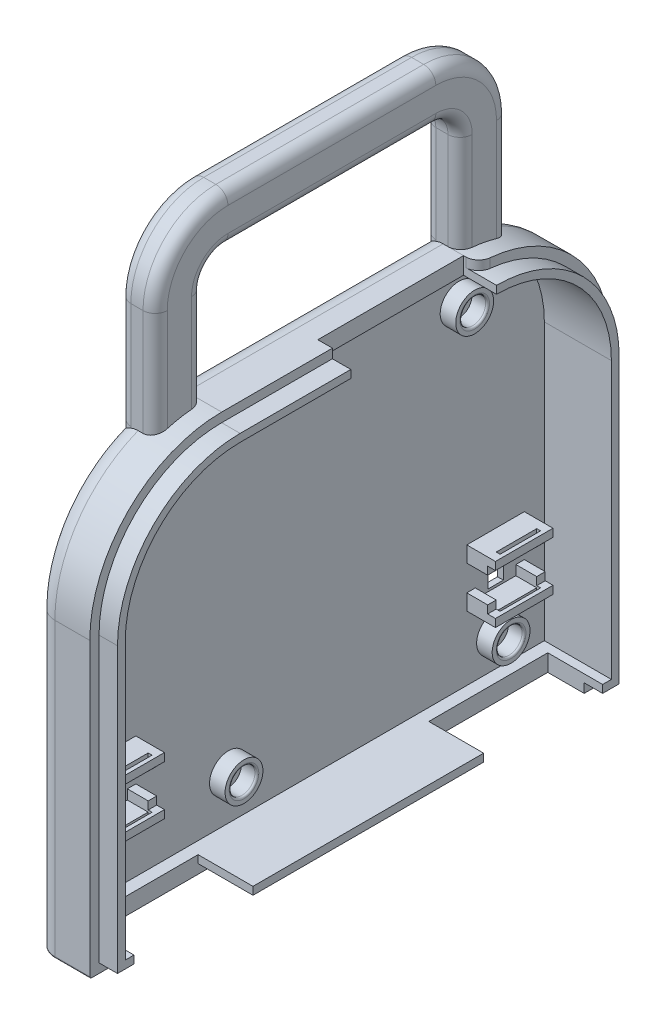
SolidWorks part; units mm, degrees
ref_plane "Front Plane" through (0, 0, 0) normal (0, 0, 1) x (1, 0, 0)
ref_plane "Top Plane" through (0, 0, 0) normal (0, 1, 0) x (1, 0, 0)
ref_plane "Right Plane" through (0, 0, 0) normal (1, 0, 0) x (0, 0, -1)
sketch "Sketch1" plane through (0, 0, 0) normal (1, 0, 0) x (0, 0, -1)
  line L0 (-52.8, 99.65) -> (52.8, 99.65)
  line L1 (-107.1, 45.35) -> (-107.1, -45.35)
  line L2 (-70, -75.35) -> (70, -75.35)
  line L3 (107.1, 45.35) -> (107.1, -45.35)
  line L4 (107.1, 0) -> (-107.1, 0) construction
  line L5 (0, 99.65) -> (0, -75.35) construction
  line L11 (107.1, -45.35) -> (107.1, -75.35)
  line L12 (107.1, -75.35) -> (70, -75.35)
  line L13 (-83.2, -21.7) -> (-76.8, -21.7)
  line L14 (-83.2, -21.7) -> (-83.2, -38.3)
  line L15 (-83.2, -38.3) -> (-76.8, -38.3)
  line L16 (-76.8, -21.7) -> (-76.8, -38.3)
  line L17 (-83.2, -21.7) -> (-76.8, -38.3) construction
  line L18 (-83.2, -38.3) -> (-76.8, -21.7) construction
  line L19 (76.8, -21.7) -> (83.2, -21.7)
  line L20 (76.8, -21.7) -> (76.8, -38.3)
  line L21 (76.8, -38.3) -> (83.2, -38.3)
  line L22 (83.2, -21.7) -> (83.2, -38.3)
  line L23 (76.8, -21.7) -> (83.2, -38.3) construction
  line L24 (76.8, -38.3) -> (83.2, -21.7) construction
  line L25 (80, -30) -> (-80, -30) construction
  line L27 (-107.1, -45.35) -> (-107.1, -75.35)
  line L28 (-107.1, -75.35) -> (-70, -75.35)
  arc A0 (52.8, 99.65) -> (107.1, 45.35) centre (52.8, 45.35) cw
  arc A1 (-52.8, 99.65) -> (-107.1, 45.35) centre (-52.8, 45.35) ccw
  point P16 (0, 0)
  point P17 (-80, -30)
  point P32 (80, -30)
  point P39 (-80, -30)
  point P40 (0, -30)
  dimension "D4" = 54.3
  dimension "D2" = 175
  dimension "D3" = 214.2
  dimension "D5" = 140
  dimension "D6" = 30
  dimension "D7" = 160
  dimension "D8" = 6.4
  dimension "D9" = 16.6
  dimension "D10" = 6.4
  dimension "D11" = 16.6
  dimension "D12" = 30
extrude "Boss-Extrude1" add sketch "Sketch1" along normal blind 2.4
sketch "Sketch9" plane through (2.4, 0, 0) normal (1, 0, 0) x (0, 0, -1)
  line L17 (52.8, 99.65) -> (-52.8, 99.65)
  line L31 (52.8, 99.65) -> (-52.8, 99.65)
  line L32 (-107.1, 45.35) -> (-107.1, -75.35)
  line L33 (-107.1, 45.35) -> (-107.1, -75.35)
  line L34 (-107.1, -75.35) -> (107.1, -75.35)
  line L39 (107.1, -75.35) -> (107.1, 45.35)
  line L43 (107.1, -75.35) -> (107.1, 45.35)
  line L45 (-107.1, -75.35) -> (107.1, -75.35)
  arc A15 (-52.8, 99.65) -> (-107.1, 45.35) centre (-52.8, 45.35) ccw
  arc A16 (-52.8, 99.65) -> (-107.1, 45.35) centre (-52.8, 45.35) ccw
  arc A17 (107.1, 45.35) -> (52.8, 99.65) centre (52.8, 45.35) ccw
  arc A18 (107.1, 45.35) -> (52.8, 99.65) centre (52.8, 45.35) ccw
  dimension "D1" = 0
sketch "Sketch10" plane through (2.4, 0, 0) normal (1, 0, 0) x (0, 0, -1)
  line L0 (65, -55.35) -> (0, -55.35) construction
  line L1 (-65, -55.35) -> (65, -55.35) construction
  line L2 (-65, -55.35) -> (-65, 54.65) construction
  line L3 (-65, 54.65) -> (65, 54.65) construction
  line L4 (65, -55.35) -> (65, 54.65) construction
  line L5 (-65, -55.35) -> (65, 54.65) construction
  line L6 (-65, 54.65) -> (65, -55.35) construction
  line L7 (0, -55.35) -> (-65, -55.35) construction
  line L8 (-107.1, -75.35) -> (107.1, -75.35) construction
  line L9 (0, -0.35) -> (0, 0) construction
  line L10 (0, -0.35) -> (0, -50.35) construction
  line L11 (-65, 54.65) -> (-65, 70.65) construction
  line L12 (-65, 70.65) -> (-70, 70.65) construction
  line L13 (0, -50.35) -> (-30, -50.35) construction
  circle A11 centre (-30, -50.35) radius 2.3
  circle A13 centre (65, 69.65) radius 2.3
  circle A14 centre (80, -55.35) radius 2.3
  circle A15 centre (-70, 70.65) radius 2.3
  point P0 (0, -0.35)
  point P11 (0, -55.35)
  point P12 (32.5, -55.35)
  point P14 (-32.5, -55.35)
  dimension "D3" = 15
  dimension "D4" = 20
  dimension "D8" = 4.6
  dimension "D1" = 130
  dimension "D2" = 110
  dimension "D5" = 50
  dimension "D6" = 15
  dimension "D7" = 16
  dimension "D9" = 5
  dimension "D10" = 30
extrude "Cut-Extrude1" cut sketch "Sketch10" against normal blind 100 and the other way blind 1000
sketch "Sketch12" plane through (2.4, 0, 0) normal (1, 0, 0) x (0, 0, -1)
  line L5 (-88.35, -38.3) -> (-88.35, -35.3)
  line L6 (-88.35, -38.3) -> (-88.35, -21.7) construction
  line L22 (71.65, -38.3) -> (71.65, -35.3)
  line L23 (71.65, -38.3) -> (71.65, -21.7) construction
  line L24 (71.65, -38.3) -> (88.35, -38.3) construction
  line L25 (88.35, -38.3) -> (88.35, -21.7) construction
  line L26 (71.65, -21.7) -> (88.35, -21.7) construction
  line L27 (71.65, -38.3) -> (88.35, -21.7) construction
  line L28 (88.35, -38.3) -> (71.65, -21.7) construction
  line L29 (71.65, -21.7) -> (71.65, -24.7)
  line L30 (88.35, -38.3) -> (88.35, -35.3)
  line L31 (88.35, -21.7) -> (88.35, -24.7)
  line L32 (71.65, -21.7) -> (88.35, -21.7) construction
  line L33 (88.35, -38.3) -> (71.65, -38.3) construction
  line L34 (88.35, -35.3) -> (91.85, -35.3)
  line L35 (71.65, -35.3) -> (68.15, -35.3)
  line L36 (68.15, -35.3) -> (68.15, -41.8)
  line L37 (68.15, -41.8) -> (91.85, -41.8)
  line L38 (91.85, -41.8) -> (91.85, -35.3)
  line L39 (71.65, -24.7) -> (68.15, -24.7)
  line L40 (68.15, -24.7) -> (68.15, -18.2)
  line L41 (68.15, -18.2) -> (91.85, -18.2)
  line L42 (91.85, -18.2) -> (91.85, -24.7)
  line L43 (91.85, -24.7) -> (88.35, -24.7)
  line L44 (83.2, -38.3) -> (76.8, -21.7) construction
  line L45 (83.2, -21.7) -> (76.8, -38.3) construction
  line L46 (-88.35, -38.3) -> (-71.65, -38.3) construction
  line L47 (-71.65, -38.3) -> (-71.65, -21.7) construction
  line L48 (-88.35, -21.7) -> (-71.65, -21.7) construction
  line L49 (-88.35, -38.3) -> (-71.65, -21.7) construction
  line L50 (-71.65, -38.3) -> (-88.35, -21.7) construction
  line L51 (-88.35, -21.7) -> (-88.35, -24.7)
  line L52 (-71.65, -38.3) -> (-71.65, -35.3)
  line L53 (-71.65, -21.7) -> (-71.65, -24.7)
  line L54 (-88.35, -21.7) -> (-71.65, -21.7) construction
  line L55 (-71.65, -38.3) -> (-88.35, -38.3) construction
  line L56 (-71.65, -35.3) -> (-68.15, -35.3)
  line L57 (-88.35, -35.3) -> (-91.85, -35.3)
  line L58 (-91.85, -35.3) -> (-91.85, -41.8)
  line L59 (-91.85, -41.8) -> (-68.15, -41.8)
  line L60 (-68.15, -41.8) -> (-68.15, -35.3)
  line L61 (-88.35, -24.7) -> (-91.85, -24.7)
  line L62 (-91.85, -24.7) -> (-91.85, -18.2)
  line L63 (-91.85, -18.2) -> (-68.15, -18.2)
  line L64 (-68.15, -18.2) -> (-68.15, -24.7)
  line L65 (-68.15, -24.7) -> (-71.65, -24.7)
  line L66 (-76.8, -38.3) -> (-83.2, -21.7) construction
  line L67 (-83.2, -38.3) -> (-76.8, -21.7) construction
  line L68 (-88.35, -21.7) -> (-88.35, -20.7047)
  line L69 (-88.35, -20.7047) -> (-71.65, -20.7047)
  line L70 (-71.65, -20.7047) -> (-71.65, -21.7)
  line L71 (-88.35, -38.3) -> (-88.35, -39.3)
  line L72 (-88.35, -39.3) -> (-71.65, -39.3)
  line L73 (-71.65, -39.3) -> (-71.65, -38.3)
  line L74 (88.35, -38.3) -> (88.35, -39.3)
  line L75 (88.35, -39.3) -> (71.65, -39.3)
  line L76 (71.65, -39.3) -> (71.65, -38.3)
  line L77 (88.35, -21.7) -> (88.35, -20.7047)
  line L78 (88.35, -20.7047) -> (71.65, -20.7047)
  line L79 (71.65, -20.7047) -> (71.65, -21.7)
  point P3 (-0.1438, 64.1533)
  point P4 (-80, -30)
  point P19 (80, -30)
  point P21 (-80, -30)
  point P30 (380.6447, 32.9453)
  point P31 (130.7088, -20.4974)
  point P32 (80, -30)
  point P49 (169.9078, -49.5925)
  dimension "D3" = 16.7
  dimension "D4" = 16.6
  dimension "D5" = 10.6
  dimension "D6" = 3.5
  dimension "D7" = 3.5
  dimension "D8" = 3.5
  dimension "D9" = 3.5
  dimension "D10" = 4.9497
  dimension "D11" = 16.7
  dimension "D12" = 16.6
  dimension "D13" = 10.6
  dimension "D14" = 3.5
  dimension "D15" = 3.5
  dimension "D16" = 3.5
  dimension "D17" = 3.5
  dimension "D18" = 4.9497
  dimension "D19" = 4.9497
  dimension "D20" = 7.3824
  dimension "D21" = 23.5468
  dimension "D22" = 24.088
  dimension "D23" = 4.9497
  dimension "D24" = 7.3824
  dimension "D25" = 23.5468
  dimension "D26" = 24.088
  dimension "D27" = 0.9953
  dimension "D28" = 1
  dimension "D29" = 1
  dimension "D30" = 0.9953
extrude "Boss-Extrude2" add sketch "Sketch12" along normal blind 8.6
sketch "Sketch14" plane through (11, 0, 0) normal (1, 0, 0) x (0, 0, -1)
  line L0 (-91.85, -18.2) -> (-91.85, -24.7) construction
  line L1 (-91.85, -18.2) -> (-68.15, -18.2)
  line L2 (-91.85, -18.2) -> (-91.85, -21.45)
  line L3 (-91.85, -21.45) -> (-68.15, -21.45)
  line L4 (-68.15, -18.2) -> (-68.15, -21.45)
  line L5 (-68.15, -18.2) -> (-91.85, -18.2) construction
  line L6 (-68.15, -24.7) -> (-68.15, -18.2) construction
  line L7 (-68.15, -41.8) -> (-68.15, -35.3) construction
  line L8 (-91.85, -41.8) -> (-68.15, -41.8)
  line L9 (-91.85, -41.8) -> (-91.85, -38.55)
  line L10 (-91.85, -38.55) -> (-68.15, -38.55)
  line L11 (-68.15, -41.8) -> (-68.15, -38.55)
  line L12 (91.85, -41.8) -> (91.85, -35.3) construction
  line L13 (68.15, -41.8) -> (91.85, -41.8)
  line L14 (68.15, -41.8) -> (68.15, -38.55)
  line L15 (68.15, -38.55) -> (91.85, -38.55)
  line L16 (91.85, -41.8) -> (91.85, -38.55)
  line L17 (91.85, -24.7) -> (91.85, -18.2) construction
  line L18 (68.15, -18.2) -> (91.85, -18.2)
  line L19 (68.15, -18.2) -> (68.15, -21.45)
  line L20 (68.15, -21.45) -> (91.85, -21.45)
  line L21 (91.85, -18.2) -> (91.85, -21.45)
extrude "Boss-Extrude3" add sketch "Sketch14" along normal blind 3.2
sketch "Sketch17" plane through (0, 0, 0) normal (1, 0, 0) x (0, 0, -1)
  line L0 (-103.9, 45.35) -> (-103.9, -72.15) construction
  line L1 (-103.9, -72.15) -> (103.9, -72.15) construction
  line L2 (103.9, -72.15) -> (103.9, 45.35) construction
  line L3 (52.8, 96.45) -> (-52.8, 96.45) construction
  line L4 (52.8, 99.65) -> (-52.8, 99.65)
  line L5 (-107.1, 45.35) -> (-107.1, -75.35)
  line L6 (-107.1, -75.35) -> (107.1, -75.35)
  line L7 (107.1, -75.35) -> (107.1, 45.35)
  line L8 (52.8, 99.65) -> (-52.8, 99.65) construction
  line L9 (-107.1, 45.35) -> (-107.1, -75.35) construction
  line L11 (107.1, -75.35) -> (107.1, 45.35) construction
  line L16 (100.1, -68.35) -> (100.1, 45.35)
  line L17 (52.8, 92.65) -> (-52.8, 92.65)
  line L18 (-100.1, 45.35) -> (-100.1, -68.35)
  line L19 (-100.1, -68.35) -> (100.1, -68.35)
  line L24 (52.8, 95.85) -> (-52.8, 95.85)
  line L25 (-103.3, 45.35) -> (-103.3, -71.55)
  line L27 (103.3, -71.55) -> (103.3, 45.35)
  line L28 (-107.1, -75.35) -> (107.1, -75.35) construction
  line L29 (-103.3, -71.55) -> (103.3, -71.55) construction
  line L31 (-103.3, -71.55) -> (103.3, -71.55)
  arc A0 (103.9, 45.35) -> (52.8, 96.45) centre (52.8, 45.35) ccw construction
  arc A1 (-52.8, 96.45) -> (-103.9, 45.35) centre (-52.8, 45.35) ccw construction
  arc A2 (-52.8, 99.65) -> (-107.1, 45.35) centre (-52.8, 45.35) ccw
  arc A3 (107.1, 45.35) -> (52.8, 99.65) centre (52.8, 45.35) ccw
  arc A4 (-52.8, 99.65) -> (-107.1, 45.35) centre (-52.8, 45.35) ccw construction
  arc A5 (107.1, 45.35) -> (52.8, 99.65) centre (52.8, 45.35) ccw construction
  arc A8 (100.1, 45.35) -> (52.8, 92.65) centre (52.8, 45.35) ccw
  arc A9 (-52.8, 92.65) -> (-100.1, 45.35) centre (-52.8, 45.35) ccw
  arc A12 (-52.8, 95.85) -> (-103.3, 45.35) centre (-52.8, 45.35) ccw
  arc A13 (103.3, 45.35) -> (52.8, 95.85) centre (52.8, 45.35) ccw
  dimension "D4" = 167.4
  dimension "D5" = 206.6
  dimension "D7" = 207.8
  dimension "D8" = 214.2
  dimension "D9" = 3.2
  dimension "D2" = 3.2
  dimension "D10" = 3.2
  dimension "D11" = 3.2
  dimension "D1" = 0
  dimension "D3" = 3.2
  dimension "D6" = 0.6
extrude "Boss-Extrude4" add sketch "Sketch17" along normal blind 30
sketch "Sketch21" plane through (2.4, 0, 0) normal (1, 0, 0) x (0, 0, -1)
  line L4 (-107.1, -75.35) -> (107.1, -75.35)
  line L6 (-107.1, -75.35) -> (107.1, -75.35)
  line L8 (52.8, 99.65) -> (-52.8, 99.65)
  line L9 (-107.1, 45.35) -> (-107.1, -75.35)
  line L11 (107.1, -75.35) -> (107.1, 45.35)
  line L12 (52.8, 99.65) -> (-52.8, 99.65)
  line L13 (-107.1, 45.35) -> (-107.1, -75.35)
  line L15 (107.1, -75.35) -> (107.1, 45.35)
  arc A4 (-52.8, 99.65) -> (-107.1, 45.35) centre (-52.8, 45.35) ccw
  arc A5 (107.1, 45.35) -> (52.8, 99.65) centre (52.8, 45.35) ccw
  arc A6 (-52.8, 99.65) -> (-107.1, 45.35) centre (-52.8, 45.35) ccw
  arc A7 (107.1, 45.35) -> (52.8, 99.65) centre (52.8, 45.35) ccw
  dimension "D1" = 0
sketch "Sketch22" plane through (2.4, 0, 0) normal (1, 0, 0) x (0, 0, -1)
  line L0 (-107.1, -75.35) -> (107.1, -75.35) construction
  line L1 (-107.1, -75.35) -> (107.1, -75.35)
  line L21 (52.8, 99.65) -> (-52.8, 99.65)
  line L22 (107.1, -75.35) -> (107.1, 45.35)
  line L24 (-107.1, 45.35) -> (-107.1, -75.35)
  line L25 (52.8, 99.65) -> (-52.8, 99.65)
  line L26 (107.1, -75.35) -> (107.1, 45.35)
  line L28 (-107.1, 45.35) -> (-107.1, -75.35)
  line L44 (-103.3, -71.55) -> (103.3, -71.55)
  line L45 (103.3, -71.55) -> (103.3, 45.35)
  line L46 (52.8, 95.85) -> (-52.8, 95.85)
  line L47 (-103.3, 45.35) -> (-103.3, -71.55)
  line L48 (-103.3, -71.55) -> (103.3, -71.55)
  line L49 (103.3, -71.55) -> (103.3, 45.35)
  line L50 (52.8, 95.85) -> (-52.8, 95.85)
  line L51 (-103.3, 45.35) -> (-103.3, -71.55)
  arc A6 (-52.8, 99.65) -> (-107.1, 45.35) centre (-52.8, 45.35) ccw
  arc A7 (107.1, 45.35) -> (52.8, 99.65) centre (52.8, 45.35) ccw
  arc A8 (-52.8, 99.65) -> (-107.1, 45.35) centre (-52.8, 45.35) ccw
  arc A9 (107.1, 45.35) -> (52.8, 99.65) centre (52.8, 45.35) ccw
  arc A20 (103.3, 45.35) -> (52.8, 95.85) centre (52.8, 45.35) ccw
  arc A21 (-52.8, 95.85) -> (-103.3, 45.35) centre (-52.8, 45.35) ccw
  arc A22 (103.3, 45.35) -> (52.8, 95.85) centre (52.8, 45.35) ccw
  arc A23 (-52.8, 95.85) -> (-103.3, 45.35) centre (-52.8, 45.35) ccw
  dimension "D1" = 0
  dimension "D2" = 0
extrude "Boss-Extrude7" add sketch "Sketch22" along normal blind 20
sketch "Sketch23" plane through (0, -75.35, 0) normal (0, -1, 0) x (1, 0, 0)
  line L0 (0, 99.1) -> (0, 107.1)
  line L1 (0, 107.1) -> (8, 107.1)
  line L2 (8, -107.1) -> (0, -107.1)
  line L3 (0, -107.1) -> (0, -99.1)
  line L8 (0, 107.1) -> (0, -107.1)
  line L9 (0, -107.1) -> (22.4, -107.1)
  line L10 (22.4, -107.1) -> (22.4, 107.1)
  line L11 (22.4, 107.1) -> (0, 107.1)
  line L12 (0, 99.1) -> (0, -99.1) construction
  line L13 (8, -107.1) -> (22.4, -107.1) construction
  line L15 (22.4, 107.1) -> (8, 107.1) construction
  arc A0 (0, 99.1) -> (8, 107.1) centre (8, 99.1) cw
  arc A1 (0, -99.1) -> (8, -107.1) centre (8, -99.1) ccw
  dimension "D2" = 8
  dimension "D1" = 0
extrude "Cut-Extrude4" cut sketch "Sketch23" against normal through all
fillet "Fillet4" radius 8 3 edges at (0, 92.7258, 79.3335) (0, 99.65, 0) (0, 92.7258, -79.3335)
sketch "Sketch26" plane through (22.4, 0, 0) normal (1, 0, 0) x (0, 0, -1)
  line L1 (-47.5, -68.3365) -> (47.5, -68.3365)
  line L2 (47.5, -68.3365) -> (47.5, -71.55)
  line L6 (47.5, -71.55) -> (-47.5, -71.55)
  line L7 (-47.5, -71.55) -> (-47.5, -68.3365)
  line L8 (-103.3, -71.55) -> (103.3, -71.55) construction
  line L9 (-96.5, -79.5369) -> (96.5, -79.5369)
  line L10 (-96.5, -79.5369) -> (-96.5, -63.5631)
  line L11 (-96.5, -63.5631) -> (96.5, -63.5631)
  line L12 (96.5, -79.5369) -> (96.5, -63.5631)
  line L13 (-96.5, -79.5369) -> (96.5, -63.5631) construction
  line L14 (-96.5, -63.5631) -> (96.5, -79.5369) construction
  line L15 (107.1, -75.35) -> (107.1, 45.35) construction
  point P0 (0, -71.55)
  point P9 (0, -68.3365)
  point P13 (0, -68.3365)
  point P16 (0, -68.3365)
  dimension "D1" = 10.6
  dimension "D2" = 15.9739
  dimension "D3" = 95
  dimension "D4" = 3.2135
extrude "Cut-Extrude7" cut sketch "Sketch26" against normal blind 15 and the other way blind 20
sketch "Sketch28" plane through (0, 99.65, 0) normal (0, 1, 0) x (1, 0, 0)
  line L0 (22.4, 52.8) -> (16.4, 52.8)
  line L1 (22.4, 52.8) -> (8, 52.8) construction
  line L2 (16.4, 52.8) -> (16.4, -7.2)
  line L3 (16.4, -7.2) -> (51.1003, -7.2)
  line L4 (51.1003, -7.2) -> (51.1003, 52.8)
  line L5 (51.1003, 52.8) -> (22.4, 52.8)
  dimension "D1" = 6
  dimension "D2" = 60
extrude "Cut-Extrude8" cut sketch "Sketch28" against normal blind 10
sketch "Sketch29" plane through (0, -21.45, 0) normal (0, -1, 0) x (1, 0, 0)
  line L12 (11, -88.35) -> (11, -91.85) construction
  line L13 (11, -82.1) -> (11, -98.1)
  line L14 (11, -98.1) -> (12.5, -98.1)
  line L15 (12.5, -98.1) -> (12.5, -82.1)
  line L16 (12.5, -82.1) -> (11, -82.1)
  line L23 (2.4, 68.15) -> (14.2, 68.15)
  line L24 (2.4, 91.85) -> (2.4, 68.15)
  line L25 (14.2, 91.85) -> (2.4, 91.85)
  line L26 (14.2, 68.15) -> (14.2, 91.85)
  line L31 (2.4, 68.15) -> (14.2, 68.15) construction
  line L32 (2.4, 91.85) -> (2.4, 68.15) construction
  line L33 (14.2, 91.85) -> (2.4, 91.85) construction
  line L34 (14.2, 68.15) -> (14.2, 91.85) construction
  point P1 (11, -90.1)
  point P9 (11, -90.1)
  point P14 (11, -90.1)
  dimension "D1" = 0
  dimension "D3" = 16
  dimension "D4" = 1.5
sketch "Sketch30" plane through (2.4, 0, 0) normal (1, 0, 0) x (0, 0, -1)
  circle A0 centre (-70, 70.65) radius 5.3
  circle A1 centre (65, 69.65) radius 5.3
  circle A2 centre (-30, -50.35) radius 5.3
  circle A3 centre (80, -55.35) radius 5.3
  circle A5 centre (65, 69.65) radius 7.8
  circle A6 centre (80, -55.35) radius 7.8
  circle A7 centre (-30, -50.35) radius 7.8
  circle A8 centre (-70, 70.65) radius 7.8
  dimension "D1" = 10.6
  dimension "D2" = 15.6
extrude "Boss-Extrude8" add sketch "Sketch30" along normal blind 6.4
fillet "Fillet7" radius 0.8 4 edges at (8.8, -55.35, -85.3) (8.8, -50.35, 24.7) (8.8, 69.65, -70.3) (8.8, 70.65, 64.7)
fillet "Fillet8" radius 0.8 5 edges at (15.2, -75.35, 107.1) (2.3431, -75.35, 104.7569) (15.2, -75.35, -107.1) (2.3431, -75.35, -104.7569) (0, -75.35, 0)
sketch "Sketch31" plane through (0, 0, 0) normal (1, 0, 0) x (0, 0, -1)
  line L0 (-52.8, 99.65) -> (-52.8, 139.65)
  line L1 (-42.8, 149.65) -> (42.8, 149.65)
  line L2 (52.8, 139.65) -> (52.8, 99.65)
  line L3 (52.8, 99.65) -> (-52.8, 99.65) construction
  line L4 (-72.8, 95.8326) -> (-72.8, 139.65)
  line L5 (-42.8, 169.65) -> (42.8, 169.65)
  line L6 (72.8, 139.65) -> (72.8, 95.8326)
  arc A2 (-52.8, 99.65) -> (-107.1, 45.35) centre (-52.8, 45.35) ccw construction
  arc A3 (107.1, 45.35) -> (52.8, 99.65) centre (52.8, 45.35) ccw construction
  arc A4 (-52.8, 99.65) -> (-72.8, 95.8326) centre (-52.8, 45.35) ccw
  arc A5 (72.8, 95.8326) -> (52.8, 99.65) centre (52.8, 45.35) ccw
  arc A9 (-52.8, 139.65) -> (-42.8, 149.65) centre (-42.8, 139.65) cw
  arc A10 (42.8, 149.65) -> (52.8, 139.65) centre (42.8, 139.65) cw
  arc A11 (72.8, 139.65) -> (42.8, 169.65) centre (42.8, 139.65) ccw
  arc A12 (-42.8, 169.65) -> (-72.8, 139.65) centre (-42.8, 139.65) ccw
  point P13 (52.8, 149.65)
  dimension "D2" = 10
  dimension "D1" = 50
  dimension "D3" = 20
  dimension "D4" = 20
extrude "Boss-Extrude9" add sketch "Sketch31" along normal blind 15
fillet "Fillet9" radius 5 21 edges at (22.4, 97.75, -52.8) (0, 117.7413, -72.8) (0, 160.8632, -64.0132) (0, 117.7413, 72.8) (0, 160.8632, 64.0132) (0, 119.65, 52.8) (0, 146.7211, 49.8711) (0, 149.65, 0) (0, 146.7211, -49.8711) (15, 119.65, 52.8) (15, 119.65, -52.8) (15, 146.7211, -49.8711) (15, 149.65, 0) (15, 117.7413, -72.8) (15, 160.8632, -64.0132) (15, 169.65, 0) (15, 117.7413, 72.8) (0, 169.65, 0) (0, 119.65, -52.8) (15, 146.7211, 49.8711) (15, 160.8632, 64.0132)
sketch "Sketch32" plane through (0, 0, 0) normal (-1, 0, 0) x (0, 0, 1)
  line L0 (52.8, 99.65) -> (52.8, 91.65)
  line L1 (72.8, 95.8326) -> (72.8, 87.1075)
  line L2 (-72.8, 95.8326) -> (-72.8, 87.1075)
  line L3 (-52.8, 99.65) -> (-52.8, 91.65)
  arc A0 (67.8, 97.5371) -> (57.8, 99.4193) centre (52.8, 45.35) ccw construction
  arc A1 (-52.8, 91.65) -> (-99.1, 45.35) centre (-52.8, 45.35) ccw construction
  arc A2 (-52.8, 99.65) -> (-57.8, 99.4193) centre (-52.8, 45.35) ccw construction
  arc A3 (-57.8, 99.4193) -> (-67.8, 97.5371) centre (-52.8, 45.35) ccw construction
  arc A4 (-67.8, 97.5371) -> (-72.8, 95.8326) centre (-52.8, 45.35) ccw construction
  arc A5 (72.8, 95.8326) -> (67.8, 97.5371) centre (52.8, 45.35) ccw construction
  arc A6 (57.8, 99.4193) -> (52.8, 99.65) centre (52.8, 45.35) ccw construction
  arc A7 (99.1, 45.35) -> (52.8, 91.65) centre (52.8, 45.35) ccw construction
  arc A8 (67.8, 97.5371) -> (57.8, 99.4193) centre (52.8, 45.35) ccw
  arc A9 (-52.8, 91.65) -> (-72.8, 87.1075) centre (-52.8, 45.35) ccw
  arc A10 (-52.8, 99.65) -> (-57.8, 99.4193) centre (-52.8, 45.35) ccw
  arc A11 (-57.8, 99.4193) -> (-67.8, 97.5371) centre (-52.8, 45.35) ccw
  arc A12 (-67.8, 97.5371) -> (-72.8, 95.8326) centre (-52.8, 45.35) ccw
  arc A13 (72.8, 95.8326) -> (67.8, 97.5371) centre (52.8, 45.35) ccw
  arc A14 (57.8, 99.4193) -> (52.8, 99.65) centre (52.8, 45.35) ccw
  arc A15 (72.8, 87.1075) -> (52.8, 91.65) centre (52.8, 45.35) ccw
extrude "Boss-Extrude10" add sketch "Sketch32" against normal up to body separate body
fillet "Fillet10" radius 5 4 edges at (0, 91.47, 72.8) (0, 95.65, 52.8) (0, 95.65, -52.8) (0, 91.47, -72.8)
sketch "Sketch33" plane through (0, -38.55, 0) normal (0, 1, 0) x (1, 0, 0)
  line L0 (11, 91.85) -> (11, 88.35) construction
  line L1 (11, 88.35) -> (11, 71.65) construction
  line L2 (11, 71.65) -> (11, 68.15) construction
  line L3 (11, 68.15) -> (14.2, 68.15) construction
  line L4 (14.2, 68.15) -> (14.2, 91.85) construction
  line L5 (14.2, 91.85) -> (11, 91.85) construction
  line L6 (11, -68.15) -> (11, -71.65) construction
  line L7 (11, -71.65) -> (11, -88.35) construction
  line L8 (11, -88.35) -> (11, -91.85) construction
  line L9 (11, -91.85) -> (14.2, -91.85) construction
  line L10 (14.2, -91.85) -> (14.2, -68.15) construction
  line L11 (14.2, -68.15) -> (11, -68.15) construction
  line L12 (11, 91.85) -> (11, 88.35) construction
  line L13 (11, 88.35) -> (11, 71.65)
  line L14 (11, 71.65) -> (11, 68.15) construction
  line L15 (11, 68.15) -> (14.2, 68.15) construction
  line L16 (14.2, 68.15) -> (14.2, 91.85) construction
  line L17 (14.2, 91.85) -> (11, 91.85) construction
  line L18 (11, -68.15) -> (11, -71.65) construction
  line L19 (11, -71.65) -> (11, -88.35)
  line L20 (11, -88.35) -> (11, -91.85) construction
  line L21 (11, -91.85) -> (14.2, -91.85) construction
  line L22 (14.2, -91.85) -> (14.2, -68.15) construction
  line L23 (14.2, -68.15) -> (11, -68.15) construction
  line L24 (11, -88.35) -> (12.6001, -88.35)
  line L25 (12.6001, -88.35) -> (12.6001, -71.65)
  line L26 (12.6001, -71.65) -> (11, -71.65)
  line L27 (11, 71.65) -> (12.6001, 71.65)
  line L28 (12.6001, 71.65) -> (12.6001, 88.35)
  line L29 (12.6001, 88.35) -> (11, 88.35)
  dimension "D1" = 1.6001
  dimension "D2" = 1.6001
extrude "Cut-Extrude9" cut sketch "Sketch33" against normal up to surface and the other way up to surface up to face at (8.3, -41.8, -80) other way up to face at (8.3, -18.2, -80)
